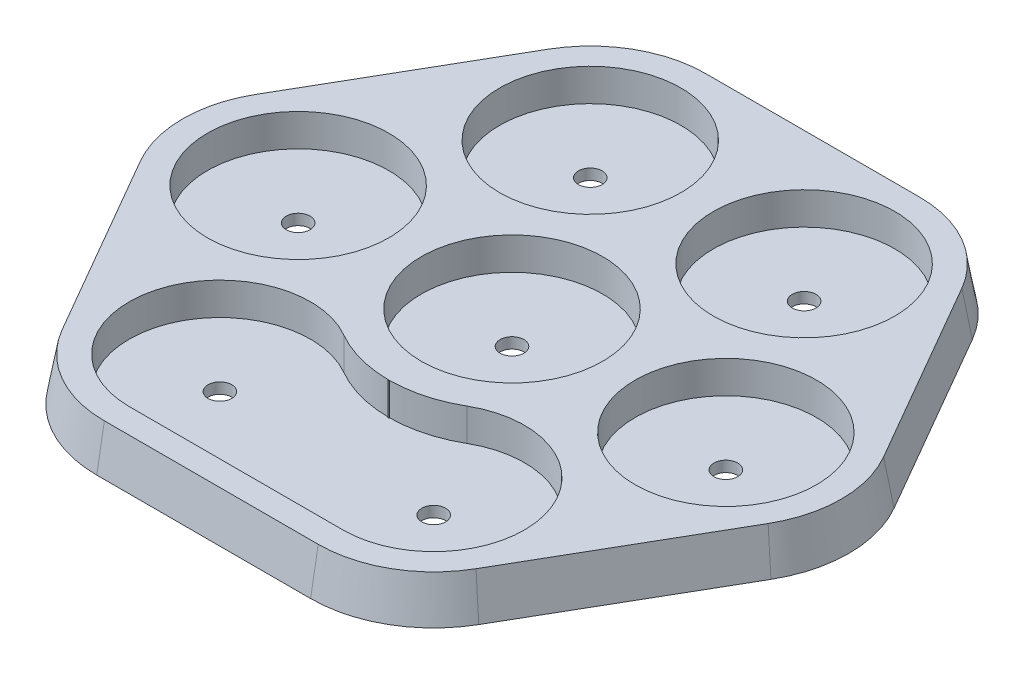
SolidWorks part; units mm, degrees
note: The reader was unsure of these and kept them because the rebuilt part matched: shared geometry of "Sketch1<3>", "Sketch1<4>".
ref_plane "Front Plane" through (0, 0, 0) normal (0, 0, 1) x (1, 0, 0)
ref_plane "Top Plane" through (0, 0, 0) normal (0, 1, 0) x (1, 0, 0)
ref_plane "Right Plane" through (0, 0, 0) normal (1, 0, 0) x (0, 0, -1)
sketch "Sketch1" plane through (0, 0, 0) normal (0, 1, 0) x (1, 0, 0)
  line L0 (0, 0) -> (-9.9, -17.1473) construction
  line L1 (-9.9, -17.1473) -> (-19.8, 0) construction
  line L2 (-19.8, 0) -> (0, 0) construction
  line L3 (9.8727, -5.7) -> (-0.0273, -22.8473)
  line L4 (-9.9, -28.5473) -> (-29.7, -28.5473)
  line L5 (-49.4727, -5.7) -> (-39.5727, -22.8473)
  line L6 (-9.9, -17.1473) -> (-29.7, -17.1473) construction
  line L7 (-29.7, -17.1473) -> (-19.8, 0) construction
  line L8 (-9.9, -8.7473) -> (-29.7, -8.7473)
  line L9 (0, 0) -> (-9.9, 17.1473) construction
  line L10 (-19.8, 0) -> (-39.6, 0) construction
  line L11 (-39.6, 0) -> (-29.7, -17.1473) construction
  line L12 (-9.9, 17.1473) -> (-19.8, 0) construction
  line L13 (-19.8, 0) -> (-29.7, 17.1473) construction
  line L14 (-29.7, 17.1473) -> (-39.6, 0) construction
  line L15 (-0.0273, 22.8473) -> (9.8727, 5.7)
  line L16 (-9.9, 17.1473) -> (-29.7, 17.1473) construction
  line L17 (-9.9, 28.5473) -> (-29.7, 28.5473)
  line L18 (-39.5727, 22.8473) -> (-49.4727, 5.7)
  line L19 (-9.9, -25.5473) -> (-29.7, -25.5473)
  circle A0 centre (0, 0) radius 8.4
  circle A1 centre (-19.8, 0) radius 8.4
  circle A2 centre (-9.9, -17.1473) radius 8.4
  circle A3 centre (-9.9, -17.1473) radius 1.1
  circle A4 centre (-19.8, 0) radius 1.1
  circle A5 centre (0, 0) radius 1.1
  circle A6 centre (-9.9, -17.1473) radius 11.4
  circle A7 centre (-19.8, 0) radius 11.4
  circle A8 centre (0, 0) radius 11.4
  circle A9 centre (-29.7, -17.1473) radius 1.1
  circle A10 centre (-29.7, -17.1473) radius 8.4
  circle A11 centre (-29.7, -17.1473) radius 11.4
  circle A12 centre (-39.6, 0) radius 1.1
  circle A13 centre (-39.6, 0) radius 8.4
  circle A14 centre (-39.6, 0) radius 11.4
  circle A15 centre (-9.9, 17.1473) radius 1.1
  circle A16 centre (-9.9, 17.1473) radius 8.4
  circle A17 centre (-9.9, 17.1473) radius 11.4
  circle A18 centre (-29.7, 17.1473) radius 1.1
  circle A19 centre (-29.7, 17.1473) radius 8.4
  circle A20 centre (-29.7, 17.1473) radius 11.4
  dimension "D1" = 16.8
  dimension "D4" = 16.8
  dimension "D5" = 16.8
  dimension "D7" = 2.2
  dimension "D8" = 2.2
  dimension "D9" = 2.2
  dimension "D10" = 22.8
  dimension "D11" = 22.8
  dimension "D12" = 22.8
  dimension "D14" = 2.2
  dimension "D15" = 16.8
  dimension "D16" = 22.8
  dimension "D18" = 16.8
  dimension "D19" = 22.8
  dimension "D20" = 2.2
  dimension "D22" = 2.2
  dimension "D23" = 22.8
  dimension "D24" = 16.8
  dimension "D29" = 2.2
  dimension "D30" = 22.8
  dimension "D31" = 16.8
  dimension "D2" = 60
  dimension "D3" = 60
  dimension "D6" = 19.8
  dimension "D13" = 60
  dimension "D17" = 60
  dimension "D21" = 60
  dimension "D25" = 60
  dimension "D26" = 60
  dimension "D27" = 60
  dimension "D28" = 60
extrude "Boss-Extrude1" add sketch "Sketch1" along normal blind 4 draft 10
extrude "Cut-Extrude1" cut sketch "Sketch1<3>" against normal blind 4 from surface at 4 contours A3 | A5 | A9 | A12 | A15 | A18 | A4 starting at face at (-19.8, 4, 0)
sketch "Sketch1<3>" plane through (0, 0, 0) normal (0, 1, 0) x (1, 0, 0) same geometry as "Sketch1"
extrude "Cut-Extrude2" cut sketch "Sketch1<4>" against normal blind 3 from surface at 4 contours A1 A4 | A2 A3 | A0 A5 | A10 A9 | A13 A12 | A16 A15 | A19 A18 | A11 A6 L19 A2 | A11 L19 A6 | L19 A11 A6 A10 | A6 A11 | A11 A2 A7 A6 | A6 A11 A7 A10
sketch "Sketch1<4>" plane through (0, 0, 0) normal (0, 1, 0) x (1, 0, 0) same geometry as "Sketch1"
